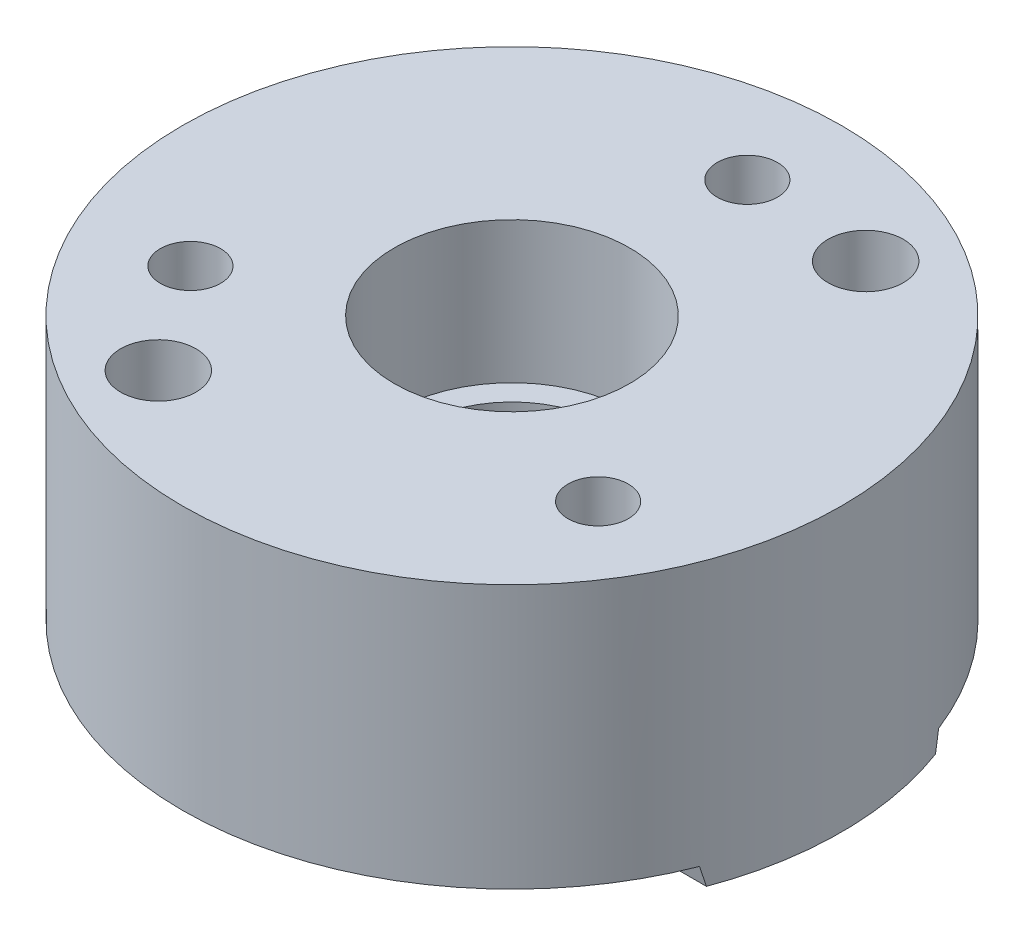
SolidWorks part; units mm, degrees
material "K110"
ref_plane "Front Plane" through (0, 0, 0) normal (0, 0, 1) x (1, 0, 0)
ref_plane "Top Plane" through (0, 0, 0) normal (0, 1, 0) x (1, 0, 0)
ref_plane "Right Plane" through (0, 0, 0) normal (1, 0, 0) x (0, 0, -1)
sketch "Sketch1" plane through (0, 0, 0) normal (0, 1, 0) x (1, 0, 0)
  circle A0 centre (0, 0) radius 35
  circle A1 centre (0, 0) radius 10
  dimension "D1" = 20
  dimension "D2" = 70
extrude "Boss-Extrude1" add sketch "Sketch1" against normal blind 30
sketch "Sketch4" plane through (0, 0, 0) normal (0, 1, 0) x (1, 0, 0)
  circle A0 centre (0, 0) radius 12.5
  dimension "D1" = 25
extrude "Cut-Extrude2" cut sketch "Sketch4" against normal blind 15
hole_wizard "CBORE for M6 Hex Socket Head Cap Screw1" positions "Sketch15" profile "Sketch8" counterbore size "M6" standard "ISO" end condition through all
sketch "Sketch15" plane through (0, -30, 0) normal (0, -1, 0) x (-1, 0, 0)
  line L0 (0, 25) -> (0, 0) construction
  line L1 (0, 0) -> (-21.6506, -12.5) construction
  line L3 (0, 0) -> (21.6506, -12.5) construction
  circle A0 centre (0, 0) radius 25 construction
  point P0 (0, 25)
  point P2 (21.6506, -12.5)
  point P4 (-21.6506, -12.5)
  dimension "D1" = 50
  dimension "D2" = 120
  dimension "D3" = 120
sketch "Sketch8" plane through (0, -30, -25) normal (1, 0, 0) x (0, 0, -1)
  line L0 (0, 0) -> (0, 30)
  line L1 (0, 30) -> (3.2, 30)
  line L3 (3.2, 30) -> (3.2, 8.4)
  line L4 (3.2, 8.4) -> (5.5, 8.4)
  line L5 (5.5, 8.4) -> (5.5, 0)
  line L7 (5.5, 0) -> (0, 0)
  line L11 (0, -6.35) -> (0, 107.95) construction
  dimension "Thru Hole Dia." = 6.4
  dimension "Thru Hole Depth" = 30
  dimension "C'Bore Dia." = 11
  dimension "C'Bore Depth" = 8.4
hole_wizard "Ø8.0mm Dowel Hole1" positions "Sketch17" profile "Sketch12" hole size "Ø8.0" standard "ISO" end condition through all
sketch "Sketch17" plane through (0, -30, 0) normal (0, -1, 0) x (-1, 0, 0)
  line L0 (-13.75, 23.8157) -> (13.75, -23.8157) construction
  line L1 (0, 35) -> (0, -35) construction
  circle A0 centre (0, 0) radius 27.5 construction
  circle A1 centre (0, 0) radius 35 construction
  point P0 (13.75, -23.8157)
  point P2 (-13.75, 23.8157)
  point P26 (0, 0)
  dimension "D1" = 55
  dimension "D2" = 30
sketch "Sketch12" plane through (-13.75, -30, 23.8157) normal (1, 0, 0) x (0, 0, -1)
  line L0 (0, 0) -> (0, 30)
  line L1 (0, 30) -> (4, 30)
  line L2 (4, 30) -> (4, 0)
  line L5 (4, 0) -> (0, 0)
  line L11 (0, -6.35) -> (0, 107.95) construction
  dimension "Thru Hole Dia." = 8
  dimension "Thru Hole Depth" = 30
sketch "Sketch14" plane through (0, -30, 0) normal (0, -1, 0) x (1, 0, 0)
  line L0 (-58.6405, -12.7) -> (58.6405, -12.7) construction
  line L1 (-35, 12.7) -> (35, 12.7)
  line L2 (-35, 12.7) -> (-35, -12.7)
  line L3 (-35, -12.7) -> (35, -12.7)
  line L4 (35, 12.7) -> (35, -12.7)
  line L5 (-35, 12.7) -> (35, -12.7) construction
  line L6 (-35, -12.7) -> (35, 12.7) construction
  circle A0 centre (0, 0) radius 35 construction
  point P0 (0, 0)
extrude "Cut-Extrude3" cut sketch "Sketch14" against normal blind 2 flip side to cut
sketch "Sketch16" plane through (0, -30, 0) normal (0, -1, 0) x (1, 0, 0)
  circle A0 centre (22.5, 0) radius 4.25
  dimension "D1" = 8.5
sketch "Sketch18" plane through (0, -30, 0) normal (0, -1, 0) x (1, 0, 0)
  circle A1 centre (-25.9, 0) radius 4.25
  dimension "D1" = 8.5
extrude "Cut-Extrude5" cut sketch "Sketch18" against normal blind 6
sketch "Sketch19" plane through (0, 0, 0) normal (1, 0, 0) x (0, 0, -1)
  line L2 (-12.7, -28) -> (-12.1641, -30)
  line L3 (-12.7, -30) -> (12.7, -30) construction
  line L4 (-12.1641, -30) -> (-12.7, -30)
  line L5 (-12.7, -30) -> (-12.7, -28)
  line L6 (12.7, -28) -> (12.1641, -30)
  line L7 (12.1641, -30) -> (12.7, -30)
  line L8 (12.7, -30) -> (12.7, -28)
  dimension "D1" = 15
  dimension "D2" = 15
extrude "Cut-Extrude6" cut sketch "Sketch19" against normal through all both and the other way through all
